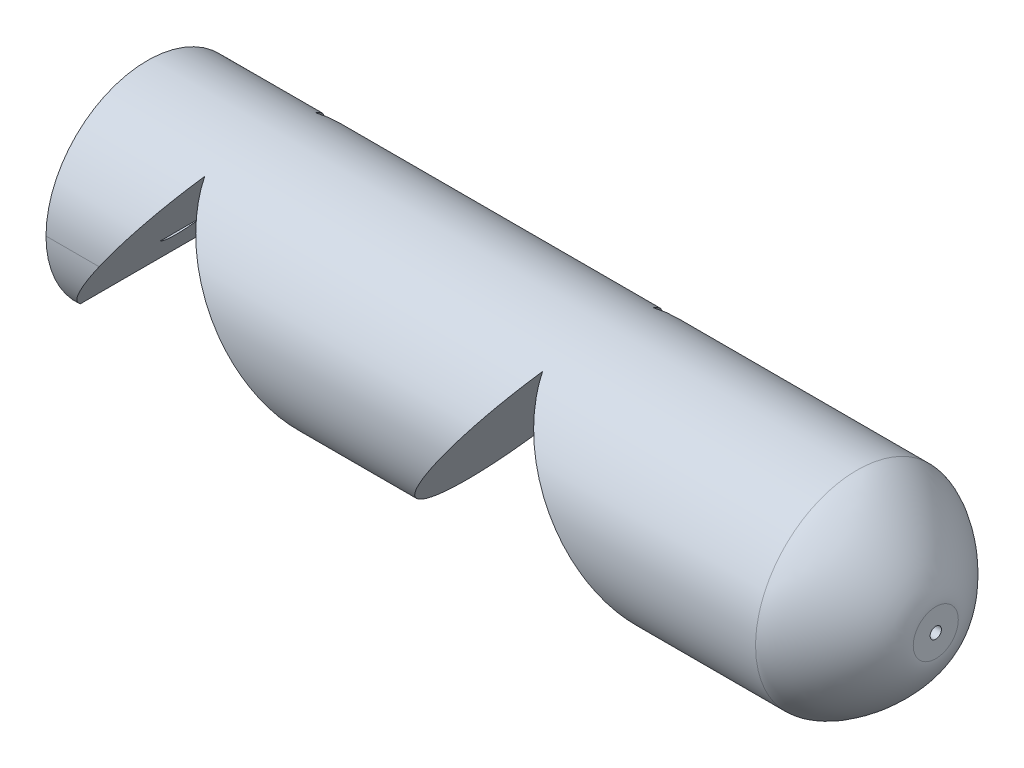
SolidWorks part; units mm, degrees
ref_plane "Front Plane" through (0, 0, 0) normal (0, 0, 1) x (1, 0, 0)
ref_plane "Top Plane" through (0, 0, 0) normal (0, 1, 0) x (1, 0, 0)
ref_plane "Right Plane" through (0, 0, 0) normal (1, 0, 0) x (0, 0, -1)
sketch "Sketch1" plane through (0, 0, 0) normal (0, 0, 1) x (1, 0, 0)
  line L1 (0, 0) -> (70, 0)
  line L2 (0, 0) -> (0, 9)
  line L3 (0, 9) -> (70, 9)
  line L4 (70, 0) -> (70, 9)
  dimension "D1" = 70
  dimension "D2" = 9
revolve "Revolve1" add sketch "Sketch1" angle 360 about L3
fillet "Fillet1" radius 7 1 edges at (70, 9, 9) conic rho 0.25
sketch "Sketch2" plane through (0, 0, 0) normal (0, 0, 1) x (1, 0, 0)
  line L0 (0, 0) -> (70, 0)
  line L1 (40, 0) -> (40, 16.5429)
  line L2 (40, 16.5429) -> (51.5835, 0)
  line L3 (40, 16.5429) -> (28.4165, 0)
  line L4 (10, 0) -> (10, 16.5429)
  line L5 (10, 16.5429) -> (21.5835, 0)
  line L6 (28.4165, 0) -> (51.5835, 0)
  line L7 (10, 16.5429) -> (-1.5835, 0)
  line L8 (-1.5835, 0) -> (21.5835, 0)
  dimension "D1" = 30
  dimension "D2" = 70
  dimension "D3" = 35
  dimension "D4" = 2
extrude "Cut-Extrude1" cut sketch "Sketch2" against normal mid plane 30 contours L1 L3 L0 | L2 L1 L0 | L0 | L5 L8 L7 region at (36.1388, 5.5143, 0) region at (13.8612, 5.5143, 0) region at (43.8612, 5.5143, 0)
ref_plane "Plane1" through (0, 0, 0) normal (-1, 0, 0) x (0, 0, 1)
sketch "Sketch4" plane through (0, 0, 0) normal (-1, 0, 0) x (0, 0, 1)
  line L0 (-5, 9) -> (5, 9) construction
  circle A0 centre (0, 9) radius 0.2
  circle A2 centre (0, 9) radius 0.2
  circle A3 centre (-5, 9) radius 0.2
  circle A4 centre (5, 9) radius 0.2 [skipped]
  point P5 (0, 9)
  dimension "D1" = 0.4
  dimension "D2" = 10
  dimension "D3" = 2
  dimension "D4" = 2
extrude "Cut-Extrude2" cut sketch "Sketch4" against normal through all contours L0 A2 | A0 L0 region at (0, 9.0849, 0) region at (0, 8.9151, 0)
ref_plane "Plane2" through (70, 0, 0) normal (1, 0, 0) x (0, 0, -1)
sketch "Sketch5" plane through (70, 0, 0) normal (1, 0, 0) x (0, 0, -1)
  circle A1 centre (0, 9) radius 0.5
  circle A2 centre (5, 9) radius 0.5
extrude "Cut-Extrude3" cut sketch "Sketch5" against normal blind 5 draft 3 contours A1 region at (70, 9, 0)
extrude "Cut-Extrude4" cut sketch "Sketch4<5>" against normal blind 40 contours A3 region at (0, 9, -5)
sketch "Sketch4<5>" plane through (0, 0, 0) normal (-1, 0, 0) x (0, 0, 1) same geometry as "Sketch4"
extrude "Cut-Extrude5" cut sketch "Sketch5<4>" against normal blind 5 draft 3 from offset 35 contours A2 region at (70, 9, -5) offset against normal yes
sketch "Sketch5<4>" plane through (70, 0, 0) normal (1, 0, 0) x (0, 0, -1) same geometry as "Sketch5"
sketch "Sketch7" plane through (0, 0, 0) normal (-1, 0, 0) x (0, 0, 1)
  circle A0 centre (0, 9) radius 3.1
  dimension "D1" = 6.2
extrude "Cut-Extrude6" cut sketch "Sketch7" against normal blind 3
